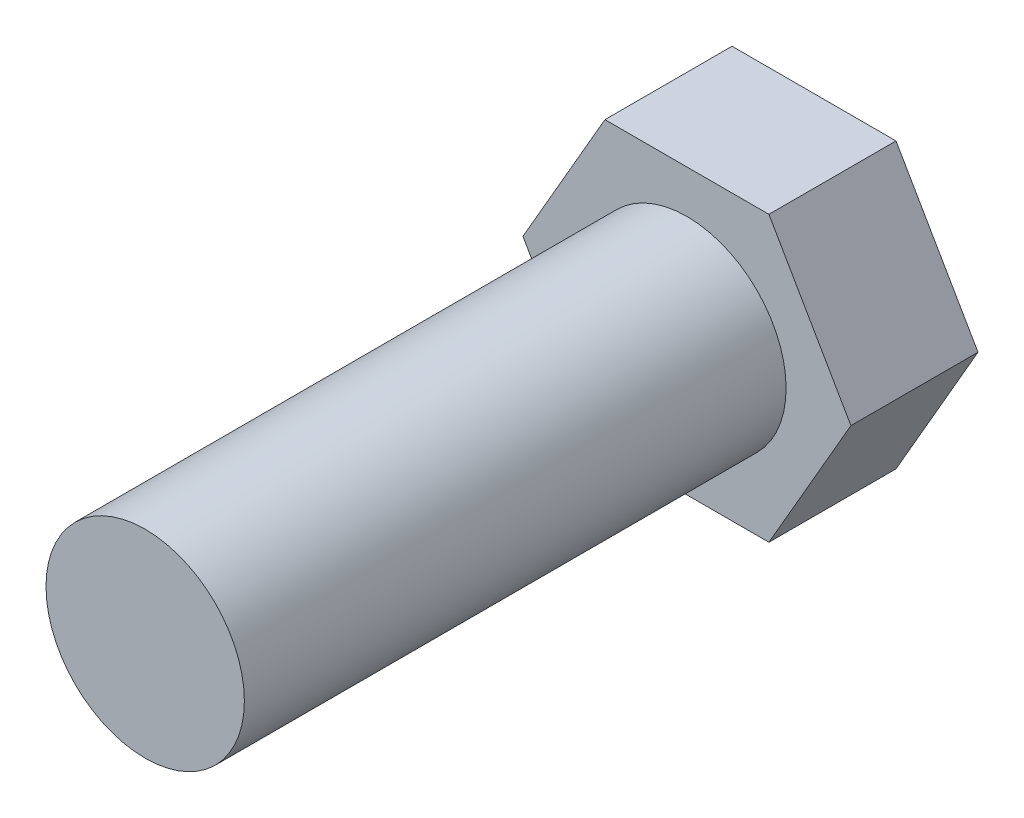
SolidWorks part; units mm, degrees
ref_plane "Alzado" through (0, 0, 0) normal (0, 0, 1) x (1, 0, 0)
ref_plane "Planta" through (0, 0, 0) normal (0, 1, 0) x (1, 0, 0)
ref_plane "Vista lateral" through (0, 0, 0) normal (1, 0, 0) x (0, 0, -1)
sketch "Sketch1" plane through (0, 0, 0) normal (0, 0, 1) x (1, 0, 0)
  line L1 (1.9675, -3.4078) -> (3.935, 0)
  line L2 (3.935, 0) -> (1.9675, 3.4078)
  line L3 (1.9675, 3.4078) -> (-1.9675, 3.4078)
  line L4 (-1.9675, 3.4078) -> (-3.935, 0)
  line L5 (-3.935, 0) -> (-1.9675, -3.4078)
  line L6 (-1.9675, -3.4078) -> (1.9675, -3.4078)
  circle A0 centre (0, 0) radius 3.4078 construction
  point P1 (0, 0)
  dimension "D1" = 7.87
extrude "Boss-Extrude1" add sketch "Sketch1" along normal blind 3.05
sketch "Sketch2" plane through (0, 0, 3.05) normal (0, 0, 1) x (1, 0, 0)
  circle A0 centre (0, 0) radius 2.38
  dimension "D1" = 4.76
extrude "Boss-Extrude2" add sketch "Sketch2" along normal blind 13
